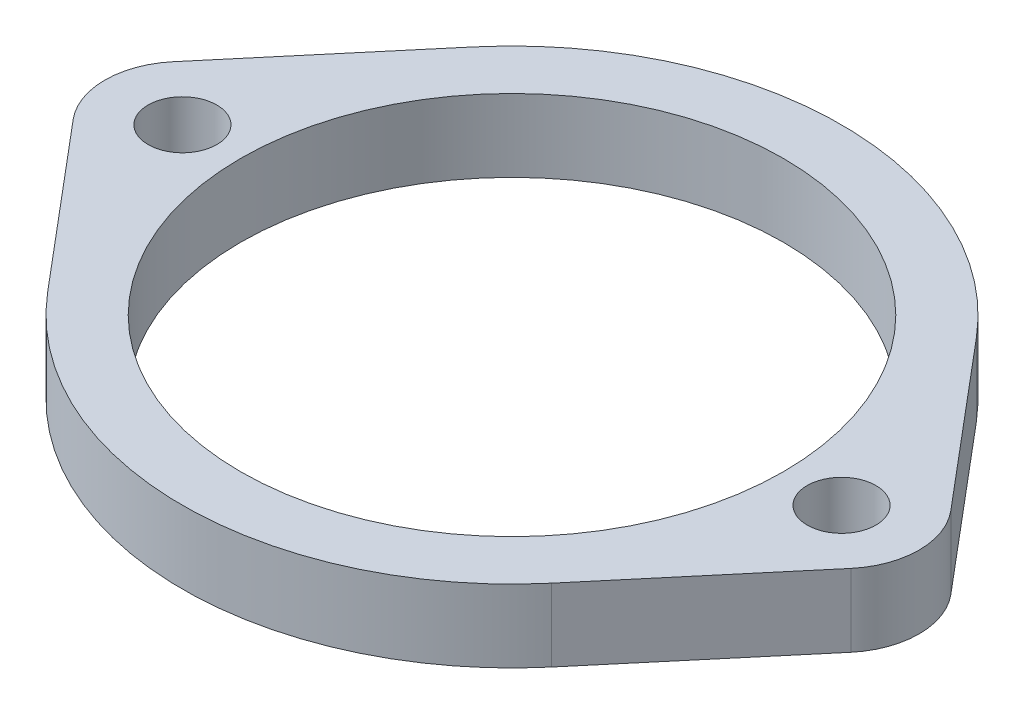
SolidWorks part; units mm, degrees
ref_plane "Front Plane" through (0, 0, 0) normal (0, 0, 1) x (1, 0, 0)
ref_plane "Top Plane" through (0, 0, 0) normal (0, 1, 0) x (1, 0, 0)
ref_plane "Right Plane" through (0, 0, 0) normal (1, 0, 0) x (0, 0, -1)
sketch "Sketch1" plane through (0, 0, 0) normal (0, 1, 0) x (1, 0, 0)
  line L0 (26.67, 43.18) -> (26.67, 0) construction
  line L1 (0, 0) -> (53.34, 0) construction
  line L2 (0, 0) -> (0, 43.18) construction
  line L3 (0, 43.18) -> (53.34, 43.18) construction
  line L4 (53.34, 0) -> (53.34, 43.18) construction
  line L5 (0, 21.59) -> (53.34, 21.59) construction
  line L6 (1.1953, 24.8634) -> (10.16, 35.5022)
  line L7 (1.1953, 18.3166) -> (10.16, 7.6778)
  line L8 (52.1447, 18.3166) -> (43.18, 7.6778)
  line L9 (52.1447, 24.8634) -> (43.18, 35.5022)
  circle A0 centre (5.08, 21.59) radius 2.25
  circle A1 centre (48.26, 21.59) radius 2.25
  circle A2 centre (26.67, 21.59) radius 17.78
  circle A3 centre (26.67, 21.59) radius 21.59 construction
  circle A4 centre (5.08, 21.59) radius 5.08 construction
  arc A5 (1.1953, 18.3166) -> (1.1953, 24.8634) centre (5.08, 21.59) cw
  arc A6 (10.16, 35.5022) -> (43.18, 35.5022) centre (26.67, 21.59) cw
  arc A7 (10.16, 7.6778) -> (43.18, 7.6778) centre (26.67, 21.59) ccw
  arc A8 (52.1447, 18.3166) -> (52.1447, 24.8634) centre (48.26, 21.59) ccw
  dimension "D3" = 4.5
  dimension "D5" = 35.56
  dimension "D6" = 43.18
  dimension "D7" = 10.16
  dimension "D1" = 43.18
  dimension "D2" = 53.34
  dimension "D4" = 21.59
extrude "Boss-Extrude1" add sketch "Sketch1" along normal blind 4.76 contours L8 A8 L9 A6 L6 A5 L7 A7 A1 A0 A2 region at (6.2024, 0, -29.7406)
